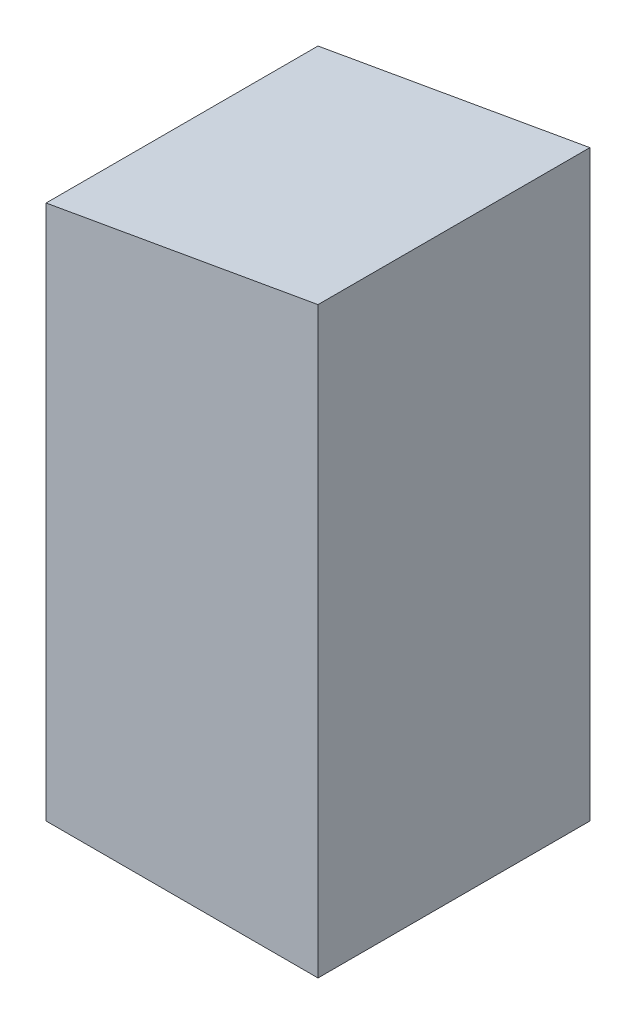
SolidWorks part; units mm, degrees
ref_plane "Front Plane" through (0, 0, 0) normal (0, 0, 1) x (1, 0, 0)
ref_plane "Top Plane" through (0, 0, 0) normal (0, 1, 0) x (1, 0, 0)
ref_plane "Right Plane" through (0, 0, 0) normal (1, 0, 0) x (0, 0, -1)
sketch "Sketch2" plane through (0, 0, 0) normal (0, 0, 1) x (1, 0, 0)
  line L0 (50.8, 108.9574) -> (0, 100)
  line L1 (0, 0) -> (50.8, 0)
  line L2 (0, 0) -> (0, 100)
  line L4 (50.8, 0) -> (50.8, 108.9574)
  dimension "D1" = 50.8
  dimension "D2" = 80
  dimension "D3" = 100
extrude "Boss-Extrude1" add sketch "Sketch2" along normal blind 50.8
